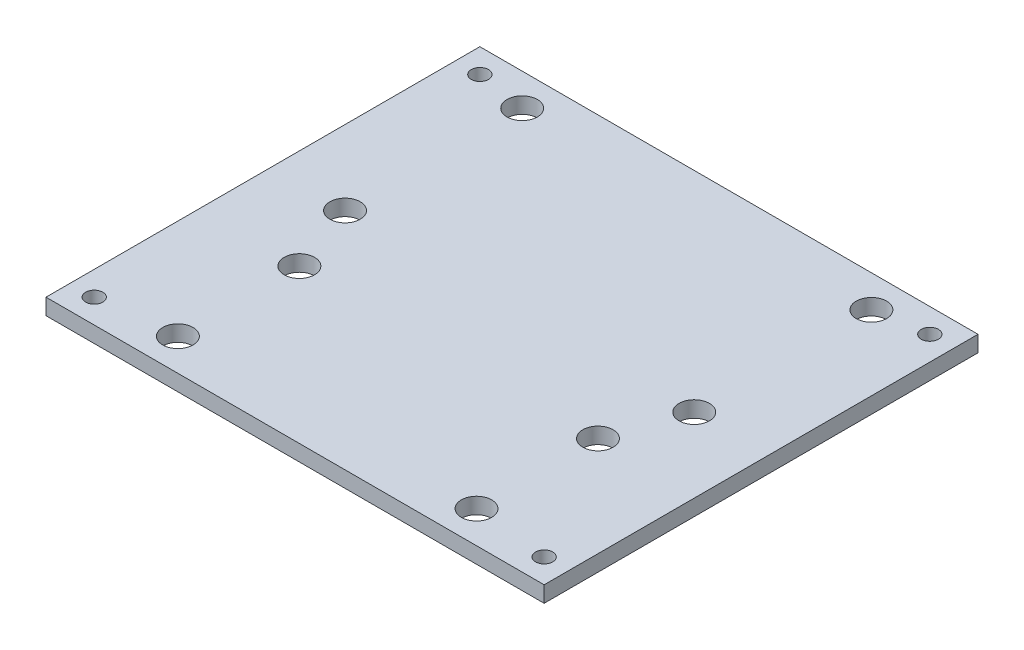
SolidWorks part; units mm, degrees
material "Polyurethane Foam Rigid"
ref_plane "Front Plane" through (0, 0, 0) normal (0, 0, 1) x (1, 0, 0)
ref_plane "Top Plane" through (0, 0, 0) normal (0, 1, 0) x (1, 0, 0)
ref_plane "Right Plane" through (0, 0, 0) normal (1, 0, 0) x (0, 0, -1)
sketch "Sketch1" plane through (0, 0, 0) normal (0, 1, 0) x (1, 0, 0)
  line L0 (-49.2125, 42.8625) -> (49.2125, 42.8625)
  line L1 (-44.45, -38.1) -> (44.45, -38.1) construction
  line L2 (-44.45, -38.1) -> (-44.45, 38.1) construction
  line L3 (-44.45, 38.1) -> (44.45, 38.1) construction
  line L4 (44.45, -38.1) -> (44.45, 38.1) construction
  line L5 (-44.45, -38.1) -> (44.45, 38.1) construction
  line L6 (-44.45, 38.1) -> (44.45, -38.1) construction
  line L7 (49.2125, -42.8625) -> (49.2125, 42.8625)
  line L8 (-49.2125, -42.8625) -> (49.2125, -42.8625)
  line L9 (-49.2125, -42.8625) -> (-49.2125, 42.8625)
  point P0 (0, 0)
  dimension "D1" = 88.9
  dimension "D2" = 76.2
  dimension "D3" = 4.7625
extrude "Boss-Extrude1" add sketch "Sketch1" along normal blind 3.175
hole_wizard "M3 Clearance Hole1" positions "3DSketch1" profile "Sketch2" hole size "M3" standard "ANSI Metric" end condition through all
sketch3d "3DSketch1"
  point P0 (-44.45, 0, 38.1)
  point P3 (44.45, 0, 38.1)
  point P6 (-44.45, 0, -38.1)
  point P9 (44.45, 0, -38.1)
sketch "Sketch2" plane through (-44.45, 0, 38.1) normal (1, 0, 0) x (0, 0, -1)
  line L0 (0, 0) -> (0, 3.175)
  line L1 (0, 3.175) -> (1.7, 3.175)
  line L2 (1.7, 3.175) -> (1.7, 0)
  line L5 (1.7, 0) -> (0, 0)
  line L11 (0, -6.35) -> (0, 107.95) construction
  dimension "Thru Hole Dia." = 3.4
  dimension "Thru Hole Depth" = 3.175
sketch "Sketch3" plane through (0, 3.175, 0) normal (0, 1, 0) x (1, 0, 0)
  line L0 (0, 19.0125) -> (0, -24.5125) construction
  line L1 (49.2125, 42.8625) -> (-49.2125, 42.8625) construction
  line L2 (-34.5, 1.5125) -> (34.5, 1.5125) construction
  line L3 (-34.5, 1.5125) -> (-34.5, 36.5125) construction
  line L4 (-34.5, 36.5125) -> (34.5, 36.5125) construction
  line L5 (34.5, 1.5125) -> (34.5, 36.5125) construction
  line L6 (-34.5, 1.5125) -> (34.5, 36.5125) construction
  line L7 (-34.5, 36.5125) -> (34.5, 1.5125) construction
  line L8 (-29.5, -12.5125) -> (29.5, -12.5125) construction
  line L9 (-29.5, -12.5125) -> (-29.5, -36.5125) construction
  line L10 (-29.5, -36.5125) -> (29.5, -36.5125) construction
  line L11 (29.5, -12.5125) -> (29.5, -36.5125) construction
  line L12 (-29.5, -12.5125) -> (29.5, -36.5125) construction
  line L13 (-29.5, -36.5125) -> (29.5, -12.5125) construction
  line L14 (-49.2125, -42.8625) -> (49.2125, -42.8625) construction
  circle A0 centre (-34.5, 36.5125) radius 3
  circle A1 centre (34.5, 36.5125) radius 3
  circle A2 centre (34.5, 1.5125) radius 3
  circle A3 centre (-34.5, 1.5125) radius 3
  circle A4 centre (-29.5, -12.5125) radius 3
  circle A5 centre (-29.5, -36.5125) radius 3
  circle A6 centre (29.5, -36.5125) radius 3
  circle A7 centre (29.5, -12.5125) radius 3
  dimension "D1" = 6
  dimension "D2" = 69
  dimension "D3" = 59
  dimension "D4" = 6.35
  dimension "D5" = 6.35
  dimension "D6" = 24
  dimension "D7" = 35
extrude "Cut-Extrude1" cut sketch "Sketch3" against normal through all
equation "\"D5@Sketch3\"=\"D4@Sketch3\""
